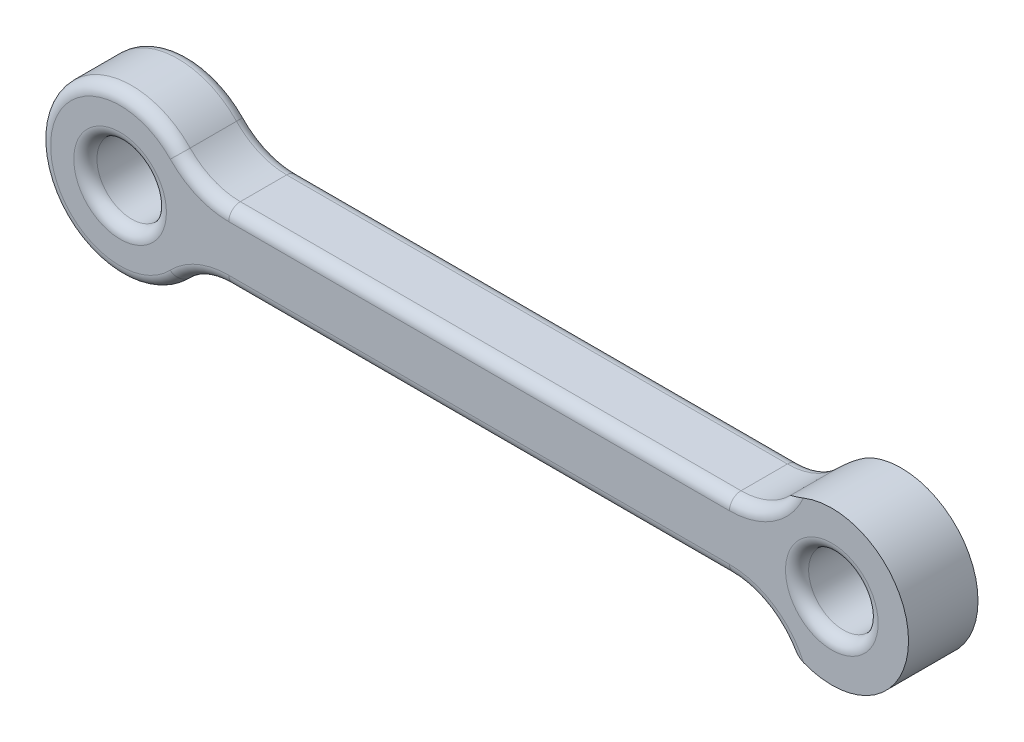
SolidWorks part; units mm, degrees
ref_plane "Front Plane" through (0, 0, 0) normal (0, 0, 1) x (1, 0, 0)
ref_plane "Top Plane" through (0, 0, 0) normal (0, 1, 0) x (1, 0, 0)
ref_plane "Right Plane" through (0, 0, 0) normal (1, 0, 0) x (0, 0, -1)
sketch "Sketch1" plane through (0, 0, 0) normal (0, 0, 1) x (1, 0, 0)
  line L0 (0, 14.0682) -> (0, -13.1713) construction
  line L1 (-12.5727, 0) -> (34.5, 0) construction
  line L2 (4.6904, 1.5) -> (26.3096, 1.5)
  line L3 (4.6904, -1.5) -> (26.3096, -1.5)
  line L4 (16.2641, 6.677) -> (16.2641, -8.0775) construction
  circle A0 centre (0, 0) radius 1.5
  arc A1 (2.5256, 2.4231) -> (2.5256, -2.4231) centre (0, 0) ccw
  circle A2 centre (30.73, 0) radius 1.5
  arc A4 (2.5256, 2.4231) -> (4.6904, 1.5) centre (4.6904, 4.5) ccw
  arc A5 (2.5256, -2.4231) -> (4.6904, -1.5) centre (4.6904, -4.5) cw
  arc A6 (26.3096, 1.5) -> (28.4744, 2.4231) centre (26.3096, 4.5) ccw
  arc A7 (26.3096, -1.5) -> (28.4744, -2.4231) centre (26.3096, -4.5) cw
  arc A8 (28.4744, -2.4231) -> (28.4744, 2.4231) centre (30.73, 0) ccw
  dimension "D1" = 30.73
  dimension "D2" = 7
  dimension "D3" = 3
  dimension "D5" = 6
  dimension "D6" = 6
  dimension "D4" = 1.5
extrude "Boss-Extrude1" add sketch "Sketch1" against normal blind 3
fillet "Fillet1" radius 0.5 17 edges at (27.4863, 1.7404, -3) (27.4863, -1.7404, -3) (15.5, -1.5, -3) (3.5137, -1.7404, -3) (-3.5, 0, -3) (3.5137, 1.7404, -3) (27.4863, 1.7404, 0) (27.4863, -1.7404, 0) (15.5, -1.5, 0) (3.5137, -1.7404, 0) (-3.5, 0, 0) (3.5137, 1.7404, 0) (1.5, 0, 0) (32.23, 0, -3) (32.23, 0, 0) (15.5, 1.5, -3) (15.5, 1.5, 0)
scale "Scale1" scale about centroid uniform scaling yes scale factor 1.9
